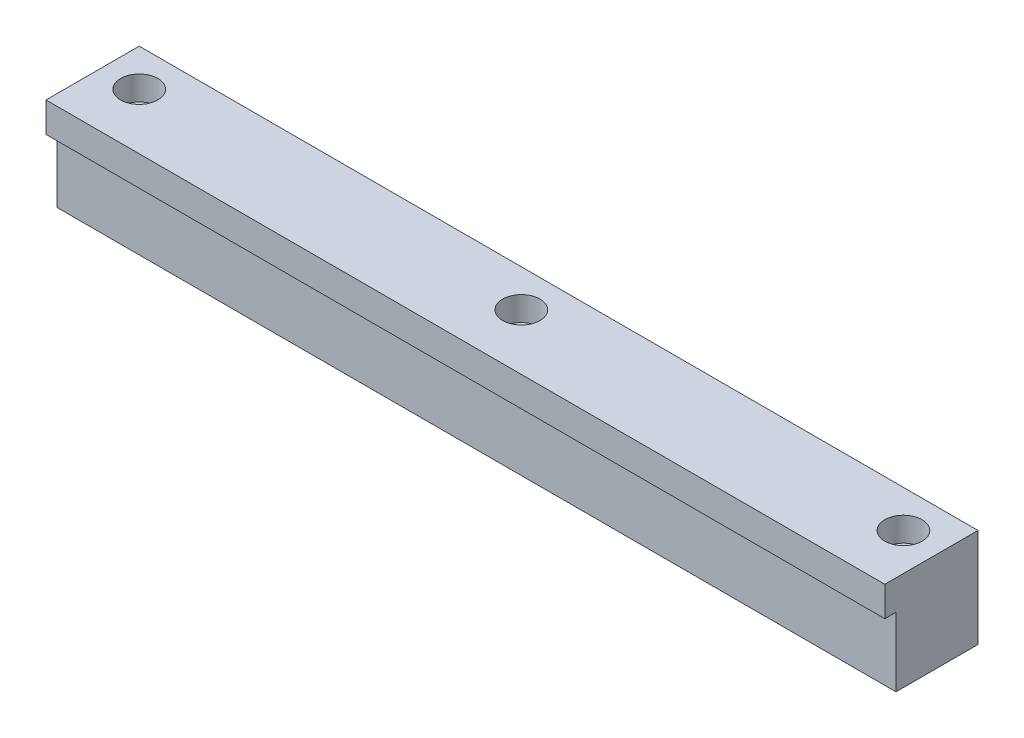
SolidWorks part; units mm, degrees
ref_plane "正面" through (0, 0, 0) normal (0, 0, 1) x (1, 0, 0)
ref_plane "平面" through (0, 0, 0) normal (0, 1, 0) x (1, 0, 0)
ref_plane "右側面" through (0, 0, 0) normal (1, 0, 0) x (0, 0, -1)
sketch "ｽｹｯﾁ1" plane through (0, 0, 0) normal (1, 0, 0) x (0, 0, -1)
  line L0 (-19, 0) -> (25, 0)
  line L1 (25, 0) -> (25, 53)
  line L2 (25, 53) -> (-25, 53)
  line L3 (-25, 53) -> (-25, 37)
  line L4 (-25, 37) -> (-19, 37)
  line L5 (-19, 37) -> (-19, 0)
extrude "ﾎﾞｽ - 押し出し1" add sketch "ｽｹｯﾁ1" against normal blind 225 and the other way blind 225
sketch "ｽｹｯﾁ2" plane through (0, 0, 0) normal (0, 1, 0) x (1, 0, 0)
  circle A0 centre (-205, 5) radius 7
  circle A1 centre (0, 5) radius 7
  circle A2 centre (205, 5) radius 7
extrude "ｶｯﾄ - 押し出し1" cut sketch "ｽｹｯﾁ2" against normal through all and the other way through all
ref_plane "平面1" through (0, 53, 0) normal (0, 1, 0) x (1, 0, 0)
sketch "ｽｹｯﾁ4" plane through (0, 53, 0) normal (0, 1, 0) x (1, 0, 0)
  circle A0 centre (-205, 5) radius 10
  circle A1 centre (0, 5) radius 10
  circle A2 centre (205, 5) radius 10
extrude "ｶｯﾄ - 押し出し2" cut sketch "ｽｹｯﾁ4" against normal blind 13
sketch "ｽｹｯﾁ5" plane through (0, 0, 0) normal (0, 1, 0) x (1, 0, 0)
  circle A0 centre (-185, 5) radius 6
  circle A1 centre (185, 5) radius 6
sketch "ｽｹｯﾁ6" plane through (0, 0, 0) normal (0, 1, 0) x (1, 0, 0)
  circle A0 centre (-185, 5) radius 6
  circle A1 centre (185, 5) radius 6
extrude "ｶｯﾄ - 押し出し4" cut sketch "ｽｹｯﾁ6" along normal blind 15
